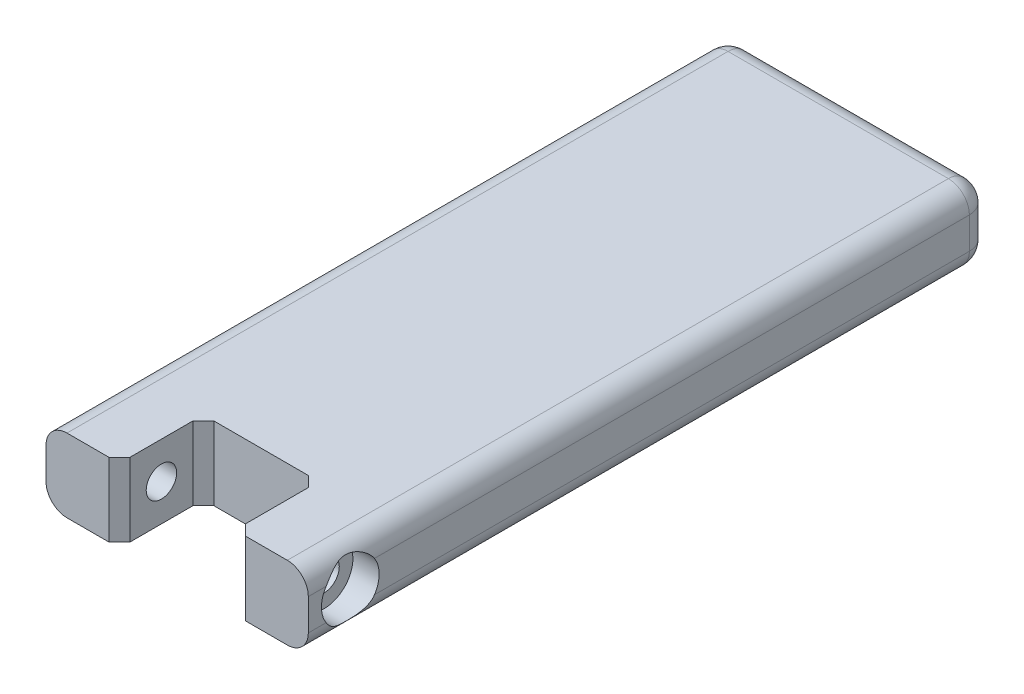
SolidWorks part; units mm, degrees
material "6061-T6 (SS)"
ref_plane "Front Plane" through (0, 0, 0) normal (0, 0, 1) x (1, 0, 0)
ref_plane "Top Plane" through (0, 0, 0) normal (0, 1, 0) x (1, 0, 0)
ref_plane "Right Plane" through (0, 0, 0) normal (1, 0, 0) x (0, 0, -1)
sketch "Sketch1" plane through (0, 0, 0) normal (0, 0, 1) x (1, 0, 0)
  line L1 (-12.5, -3.5) -> (12.5, -3.5)
  line L2 (-12.5, -3.5) -> (-12.5, 3.5)
  line L3 (-12.5, 3.5) -> (12.5, 3.5)
  line L4 (12.5, -3.5) -> (12.5, 3.5)
  line L5 (-12.5, -3.5) -> (12.5, 3.5) construction
  line L6 (-12.5, 3.5) -> (12.5, -3.5) construction
  point P0 (0, 0)
  dimension "D1" = 25
  dimension "D2" = 7
extrude "Boss-Extrude1" add sketch "Sketch1" along normal blind 65
sketch "Sketch2" plane through (0, 3.5, 0) normal (0, 1, 0) x (1, 0, 0)
  line L0 (12.5, -65) -> (-12.5, -65) construction
  line L1 (-5.5, -65) -> (5.5, -65)
  line L2 (-5.5, -65) -> (-5.5, -57)
  line L3 (-5.5, -57) -> (5.5, -57)
  line L4 (5.5, -65) -> (5.5, -57)
  line L5 (12.5, -65) -> (12.5, 0) construction
  line L6 (-12.5, -65) -> (-12.5, 0) construction
  dimension "D1" = 7
  dimension "D2" = 7
  dimension "D3" = 8
extrude "Cut-Extrude1" cut sketch "Sketch2" against normal through all
chamfer "Chamfer1" distance 1 angle 45 2 edges at (5.5, 0, 57) (-5.5, 0, 57)
hole_wizard "CBORE for M2.5 SHCS2" positions "Sketch8" profile "Sketch9" counterbore size "M2.5" standard "ANSI Metric" end condition through all
sketch "Sketch8" plane through (12.5, -6.575, 116.7065) normal (1, 0, 0) x (0, 0, -1)
  point P0 (55.7065, 6.575)
sketch "Sketch9" plane through (12.5, 0, 61) normal (0, 1, 0) x (0, 0, -1)
  line L0 (0, 0) -> (0, 25)
  line L1 (0, 25) -> (1.45, 25)
  line L3 (1.45, 25) -> (1.45, 2.5)
  line L4 (1.45, 2.5) -> (2.75, 2.5)
  line L5 (2.75, 2.5) -> (2.75, 0)
  line L7 (2.75, 0) -> (0, 0)
  line L11 (0, -6.35) -> (0, 107.95) construction
  dimension "Thru Hole Dia." = 2.9
  dimension "Thru Hole Depth" = 25
  dimension "C'Bore Dia." = 5.5
  dimension "C'Bore Depth" = 2.5
fillet "Fillet1" radius 2 4 edges at (-12.5, 3.5, 32.5) (12.5, 3.5, 32.5) (-12.5, -3.5, 32.5) (12.5, -3.5, 32.5)
fillet "Fillet2" radius 2 8 edges at (-11.9142, -2.9142, 0) (0, -3.5, 0) (11.9142, -2.9142, 0) (12.5, 0, 0) (11.9142, 2.9142, 0) (0, 3.5, 0) (-11.9142, 2.9142, 0) (-12.5, 0, 0)
chamfer "Chamfer2" distance 1 angle 45 2 edges at (5.5, 0, 65) (-5.5, 0, 65)
